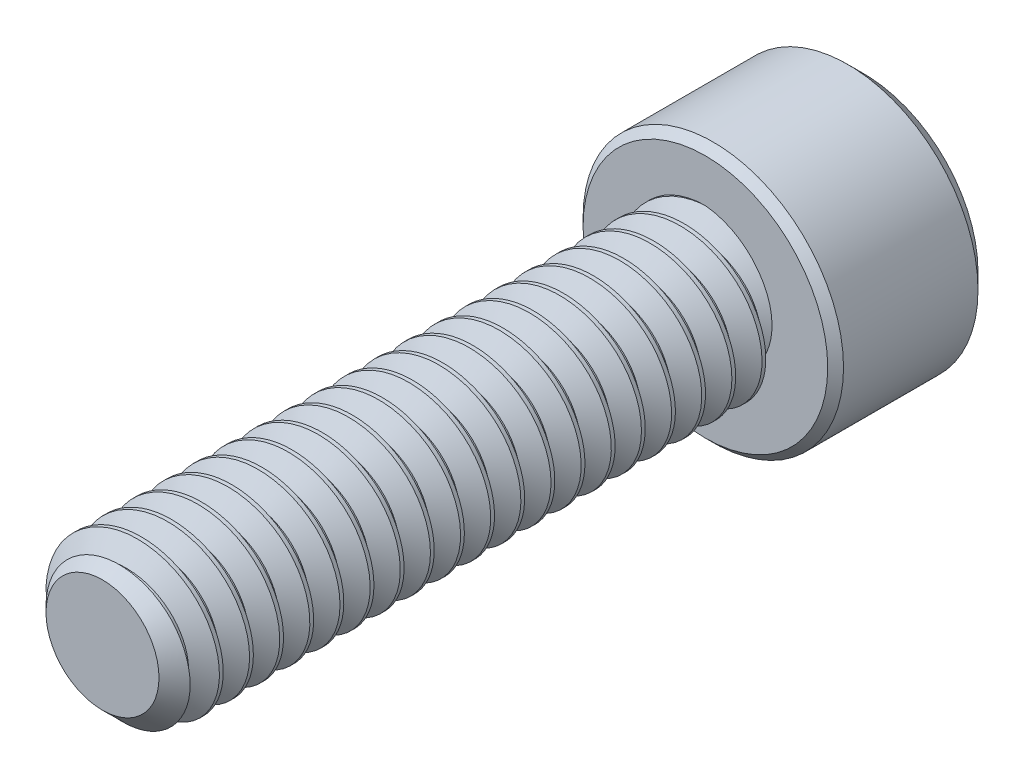
SolidWorks part; units mm, degrees
ref_plane "Front Plane" through (0, 0, 0) normal (0, 0, 1) x (1, 0, 0)
ref_plane "Top Plane" through (0, 0, 0) normal (0, 1, 0) x (1, 0, 0)
ref_plane "Right Plane" through (0, 0, 0) normal (1, 0, 0) x (0, 0, -1)
sketch "Sketch1" plane through (0, 0, 0) normal (0, 0, 1) x (1, 0, 0)
  line L0 (0, 2.0828) -> (0, -2.0828) construction
  circle A0 centre (0, 0) radius 2.0828
  dimension "OD" = 4.1656
extrude "Extrude1" add sketch "Sketch1" against normal blind 15.875
sketch "Sketch2" plane through (0, 0, 0) normal (0, 0, 1) x (1, 0, 0)
  circle A0 centre (0, 0) radius 2.0828 construction
  circle A1 centre (0, 0) radius 2.0828
curve "Helix/Spiral1" pitch 0.7937 height 16.6687 turns 21 parameters "pitch"=0.7937
chamfer "Chamfer3" distance 0.5953 angle 45 1 edges at (2.0828, 0, 0)
sketch "Sketch3" plane through (0, 0, 0) normal (1, 0, 0) x (0, 0, -1)
  line L0 (-0.6945, 2.0828) -> (-0.3969, 1.5672)
  line L1 (-0.3969, 1.5672) -> (-0.2977, 1.5672)
  line L2 (-0.2977, 1.5672) -> (0, 2.0828)
  line L3 (-0.6945, 2.0828) -> (0, 2.0828)
  line L4 (-0.3473, 2.0828) -> (-0.3473, 1.5672) construction
  line L5 (-0.5457, 1.825) -> (-0.1488, 1.825) construction
  line L6 (0, 2.0828) -> (0, -2.0828) construction
  dimension "D1" = 0.0992
  dimension "D2" = 0.3969
  dimension "D3" = 60
sweep "Cut-Sweep1" cut profiles "Sketch3" path "Helix/Spiral1"
sketch "Sketch6" plane through (0, 0, -15.875) normal (0, 0, -1) x (-1, 0, 0)
  circle A0 centre (0, 0) radius 3.429
  dimension "head dia" = 6.858
extrude "Extrude2" add sketch "Sketch6" along normal blind 4.1656
sketch "Sketch7" plane through (0, 0, -20.0406) normal (0, 0, -1) x (-1, 0, 0)
  line L1 (0, 2.0622) -> (-1.7859, 1.0311)
  line L2 (-1.7859, 1.0311) -> (-1.7859, -1.0311)
  line L3 (-1.7859, -1.0311) -> (0, -2.0622)
  line L4 (0, -2.0622) -> (1.7859, -1.0311)
  line L5 (1.7859, -1.0311) -> (1.7859, 1.0311)
  line L6 (1.7859, 1.0311) -> (0, 2.0622)
  circle A0 centre (0, 0) radius 1.7859 construction
  dimension "hex dia" = 3.5719
extrude "Cut-Extrude1" cut sketch "Sketch7" against normal blind 2.6789
sketch "Sketch8" plane through (0, 0, -20.0406) normal (0, 0, -1) x (-1, 0, 0)
  circle A0 centre (0, 0) radius 2.0622
extrude "Cut-Extrude2" cut sketch "Sketch8" against normal blind 0.4166 draft 45
chamfer "Chamfer1" distance 0.4166 angle 45 1 edges at (-3.429, 0, -20.0406)
chamfer "Chamfer2" distance 0.2083 angle 45 1 edges at (-3.429, 0, -15.875)
sketch "Sketch9" plane through (0, 0, 0) normal (1, 0, 0) x (0, 0, -1)
  line L0 (0, 2.0828) -> (0, -2.0828) construction
  line L1 (4.3656, 2.0828) -> (4.3656, -2.0828) construction
  line L2 (15.875, 3.429) -> (15.875, -3.429) construction
  line L3 (20.0406, 3.429) -> (20.0406, -3.429) construction
  line L4 (20.0406, 0) -> (0, 0) construction
  dimension "D1" = 4.3656
  dimension "D2" = 4.1656
  dimension "D3" = 6.858
  dimension "D4" = 0.635
  dimension "D5" = 0.3302
equation "\"D3@Helix/Spiral1\" = \"screw length@Extrude1\"+\"pitch@Helix/Spiral1\""
equation "\"D1@Sketch3\" = \"pitch@Helix/Spiral1\"*.125"
equation "\"D2@Sketch3\" = \"pitch@Helix/Spiral1\"*.5"
equation "\"D1@Cut-Extrude1\" = \"hex dia@Sketch7\"*.75"
equation "\"D1@Chamfer1\" = \"head depth@Extrude2\"/10"
equation "\"D1@Sketch9\" = \"pitch@Helix/Spiral1\"*5.5"
equation "\"D1@Chamfer2\" = \"D1@Chamfer1\"/2"
equation "\"D1@Cut-Extrude2\" = \"D1@Chamfer2\"*2"
equation "\"D1@Chamfer3\" = \"pitch@Helix/Spiral1\"*.750"
equation "\"D2@Sketch9\" = \"head depth@Extrude2\""
equation "\"D3@Sketch9\" = \"head dia@Sketch6\""
equation "\"D4@Sketch9\" = \"screw length@Extrude1\""
